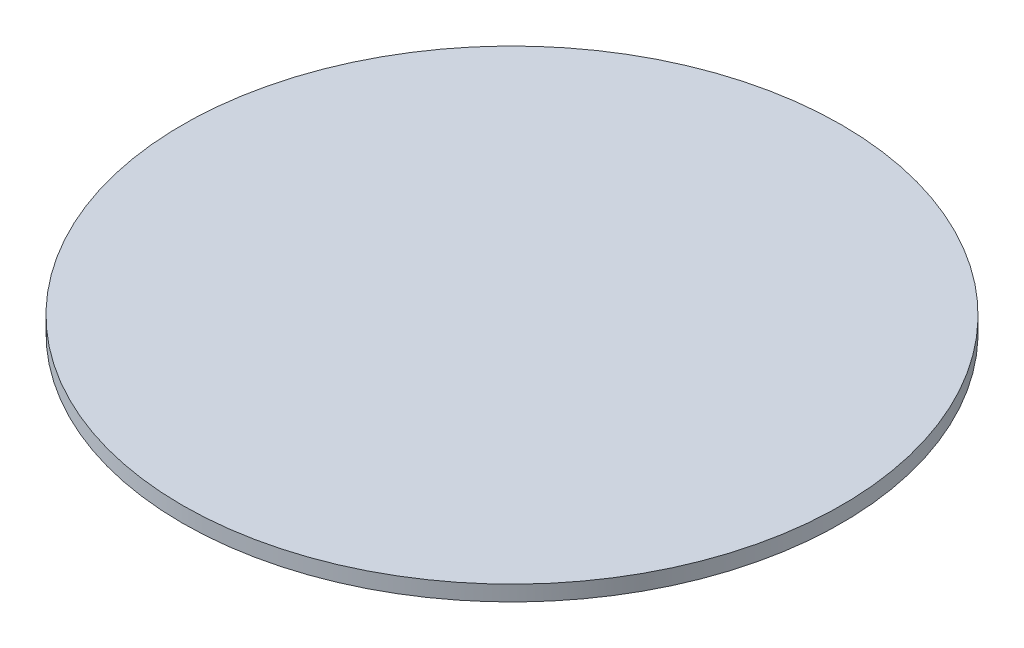
SolidWorks part; units mm, degrees
ref_plane "Plano frontal" through (0, 0, 0) normal (0, 0, 1) x (1, 0, 0)
ref_plane "Plano superior" through (0, 0, 0) normal (0, 1, 0) x (1, 0, 0)
ref_plane "Plano direito" through (0, 0, 0) normal (1, 0, 0) x (0, 0, -1)
sketch "Esboço1" plane through (0, 0, 0) normal (0, 1, 0) x (1, 0, 0)
  circle A0 centre (0, 0) radius 85.4
  dimension "D1" = 170.8
extrude "Ressalto-extrusão1" add sketch "Esboço1" along normal blind 4
